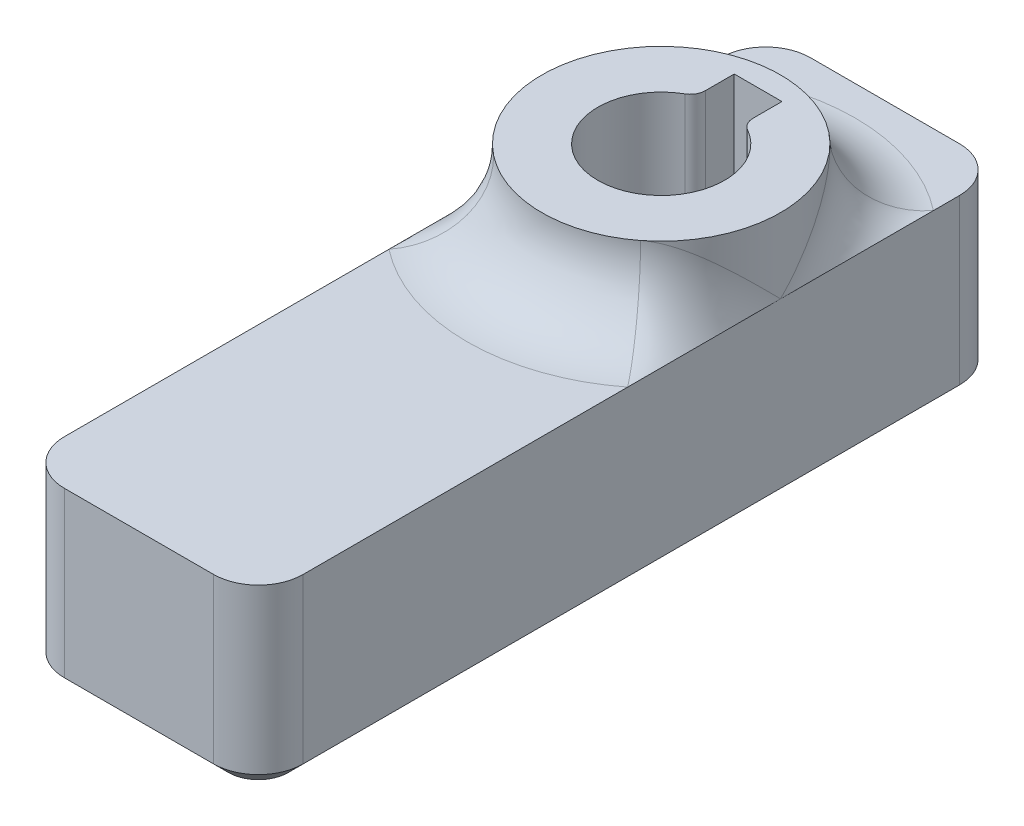
SolidWorks part; units mm, degrees
ref_plane "Спереди" through (0, 0, 0) normal (0, 0, 1) x (1, 0, 0)
ref_plane "Сверху" through (0, 0, 0) normal (0, 1, 0) x (1, 0, 0)
ref_plane "Справа" through (0, 0, 0) normal (1, 0, 0) x (0, 0, -1)
sketch "Эскиз1" plane through (0, 0, 0) normal (0, 1, 0) x (1, 0, 0)
  circle A0 centre (0, 0) radius 8
  dimension "D1" = 16
extrude "Бобышка-Вытянуть1" add sketch "Эскиз1" along normal blind 17
sketch "Эскиз5" plane through (0, 0, 0) normal (0, -1, 0) x (1, 0, 0)
  line L1 (-8, -15) -> (8, -15)
  line L2 (-8, -15) -> (-8, 35)
  line L3 (-8, 35) -> (8, 35)
  line L4 (8, -15) -> (8, 35)
  line L5 (0, 35) -> (0, -15) construction
  line L6 (-8, 0) -> (8, 0) construction
  point P0 (0, -15)
  dimension "D1" = 16
  dimension "D2" = 50
  dimension "D3" = 15
extrude "Бобышка-Вытянуть2" add sketch "Эскиз5" against normal blind 12
sketch "Эскиз3" plane through (0, 17, 0) normal (0, 1, 0) x (1, 0, 0)
  circle A0 centre (0, 0) radius 4.25
  dimension "D1" = 8.5
extrude "Вырез-Вытянуть2" cut sketch "Эскиз3" against normal blind 15
sketch "Эскиз4" plane through (0, 17, 0) normal (0, 1, 0) x (1, 0, 0)
  line L0 (0, 0) -> (-0.0075, 7.6929) construction
  line L2 (-1.6041, 2) -> (1.5959, 2)
  line L3 (-1.6041, 2) -> (-1.6041, 6.5)
  line L4 (-1.6041, 6.5) -> (1.5959, 6.5)
  line L5 (1.5959, 2) -> (1.5959, 6.5)
  line L6 (-0.0041, 6.5) -> (-0.0041, 2) construction
  line L7 (-1.6041, 4.25) -> (1.5959, 4.25) construction
  circle A0 centre (0, 0) radius 4.25 construction
  point P3 (-0.0041, 4.25)
  dimension "D1" = 4.5
  dimension "D2" = 3.2
extrude "Вырез-Вытянуть3" cut sketch "Эскиз4" against normal blind 15
fillet "Скругление2" radius 1 2 edges at (1.5959, 9.5, -3.939) (-1.6041, 9.5, -3.9356)
sketch "Эскиз6" plane through (0, 0, 0) normal (0, 1, 0) x (-1, 0, 0)
  line L0 (0, 26.287) -> (0, -16.953) construction
  line L1 (-9.4979, 10) -> (22.6058, 10) construction
  line L3 (-8, 35) -> (8, 35) construction
  circle A0 centre (0, 31) radius 2.5
  circle A1 centre (0, -11) radius 2.5
  dimension "D1" = 42
  dimension "D2" = 5
  dimension "D3" = 4
extrude "Вырез-Вытянуть4" cut sketch "Эскиз6" along normal blind 9
fillet "Скругление4" radius 3 4 edges at (8, 6, 35) (-8, 6, 35) (8, 6, -15) (-8, 6, -15)
chamfer "Фаска1" distance 1 angle 45 10 edges at (0, 0, 35) (-8, 0, 10) (0, 0, -15) (-7.1213, 0, -14.1213) (-7.1213, 0, 34.1213) (7.1213, 0, -14.1213) (7.1213, 0, 34.1213) (8, 0, 10) (0, 0, -13.5) (0, 0, 33.5)
fillet "Скругление6" radius 5 2 edges at (0, 12, 8) (0, 12, -8)
sketch "Эскиз7" plane through (0, 2, 0) normal (0, 1, 0) x (1, 0, 0)
  circle A0 centre (0, 0) radius 2
  dimension "D1" = 4
extrude "Вырез-Вытянуть5" cut sketch "Эскиз7" against normal blind 4
chamfer "Фаска2" distance 1.5 angle 45 1 edges at (0, 0, 2)
sketch "Эскиз8" plane through (-8, 0, 0) normal (-1, 0, 0) x (0, 0, 1)
  line L1 (20.8468, 4.9) -> (25.9468, 4.9)
  line L2 (20.8468, 4.9) -> (20.8468, 10)
  line L3 (20.8468, 10) -> (25.9468, 10)
  line L4 (25.9468, 4.9) -> (25.9468, 10)
  line L5 (23.3968, 10) -> (23.3968, 4.9) construction
  line L6 (20.8468, 7.45) -> (25.9468, 7.45) construction
  line L7 (32, 12) -> (10.247, 12) construction
  point P0 (23.3968, 7.45)
  dimension "D1" = 5.1
  dimension "D2" = 5.1
  dimension "D3" = 2
extrude "Вырез-Вытянуть6" [suppressed] cut sketch "Эскиз8" against normal blind 6
fillet "Скругление7" [suppressed] radius 0.5
sketch "Эскиз10" [suppressed] plane through (-2, 0, 0) normal (-1, 0, 0) x (0, 0, 1)
  line L0 (23.3968, 10) -> (23.3968, 7.45) construction
  line L1 (25.9468, 10) -> (20.8468, 10) construction
  line L2 (23.3968, 7.45) -> (20.8468, 4.9) construction
  line L3 (20.8468, 4.9) -> (25.9468, 4.9) construction
  circle A0 centre (23.3968, 7.45) radius 2
extrude "Вырез-Вытянуть8" [suppressed] cut sketch "Эскиз10" against normal through all
sketch "Эскиз9" plane through (0, 17, 0) normal (0, 1, 0) x (1, 0, 0)
  line L1 (-13.3044, -16.5088) -> (12.8714, -16.5088)
  line L2 (-13.3044, -16.5088) -> (-13.3044, 16.5088)
  line L3 (-13.3044, 16.5088) -> (12.8714, 16.5088)
  line L4 (12.8714, -16.5088) -> (12.8714, 16.5088)
  line L5 (-0.2165, 16.5088) -> (-0.2165, -16.5088) construction
  line L6 (-13.3044, 0) -> (12.8714, 0) construction
  point P0 (-0.2165, 0)
extrude "Вырез-Вытянуть7" [suppressed] cut sketch "Эскиз9" against normal blind 100
